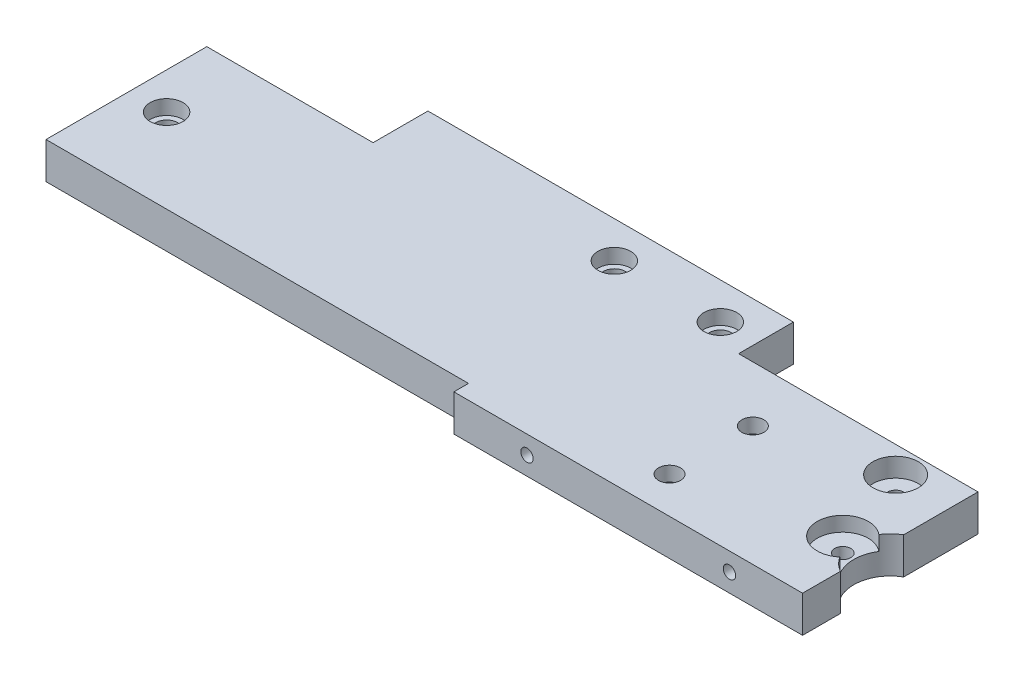
SolidWorks part; units mm, degrees
other "标注1"
sketch "草图3" plane through (0, 5, 29.5) normal (-0.6417, 0.7662, 0.0339) x (0.7661, 0.6384, 0.0747)
ref_plane "前视基准面" through (0, 0, 0) normal (0, 0, 1) x (1, 0, 0)
ref_plane "上视基准面" through (0, 0, 0) normal (0, 1, 0) x (1, 0, 0)
ref_plane "右视基准面" through (0, 0, 0) normal (1, 0, 0) x (0, 0, -1)
other "Configuration Table"
sketch "草图1" plane through (0, 0, 0) normal (0, 1, 0) x (1, 0, 0)
  line L0 (19.7074, -14.6) -> (48.9981, -14.6) construction
  line L33 (-50, -29.5) -> (0, -29.5)
  line L34 (-50, -29.5) -> (-50, 0)
  line L36 (0, -29.5) -> (0, 0)
  line L37 (-50, 0) -> (0, 0)
  line L38 (-72.75, -7.5) -> (32.75, -7.5)
  line L39 (-72.75, -7.5) -> (-72.75, -29.5)
  line L40 (-72.75, -29.5) -> (32.75, -29.5)
  line L41 (32.75, -7.5) -> (32.75, -29.5)
  line L48 (49.4474, -17.6) -> (56.141, -17.6) construction
  circle A7 centre (28.75, -22) radius 1.1
  circle A8 centre (25.0839, -11.1) radius 1.1
  circle A10 centre (25.0839, -11.1) radius 3.1
  circle A11 centre (35.25, -22) radius 5
  circle A13 centre (-19.5, -5) radius 2.25
  circle A14 centre (-19.5, -5) radius 1.5
  circle A15 centre (-5, -5) radius 1.5
  circle A16 centre (-5, -5) radius 2.25
  circle A18 centre (-67.75, -18) radius 1.5
  circle A19 centre (-67.75, -18) radius 2.25
  circle A20 centre (28.75, -22) radius 3.5
  point P0 (-90.6464, 22.0667)
  dimension "D1" = 2.2
  dimension "D2" = 29.5
  dimension "D3" = 11.5
  dimension "D4" = 50
  dimension "D5" = 6.5
  dimension "D9" = 3
  dimension "D10" = 4.5
  dimension "D13" = 6.5
  dimension "D15" = 10
  dimension "D6" = 6.2
  dimension "D17" = 7
  dimension "D7" = 4
  dimension "D8" = 2.5
  dimension "D11" = 14.5
  dimension "D12" = 5
  dimension "D14" = 5
  dimension "D16" = 5
extrude "凸台-拉伸1" add sketch "草图1" along normal blind 5 contours L34 | L37 L36 L33 L34 | L38 L41 L40 L39 region at (-61.1658, 0, 18.5164)
extrude "切除-拉伸2" cut sketch "草图1<20>" along normal through all contours A14 | A15 | A18
sketch "草图1<20>" plane through (0, 0, 0) normal (0, 1, 0) x (1, 0, 0) same geometry as "草图1"
extrude "切除-拉伸3" cut sketch "草图1<22>" against normal blind 2 from surface contours A13 | A16 | A19 starting at face at (-67.75, 5, 19.5)
sketch "草图1<22>" plane through (0, 0, 0) normal (0, 1, 0) x (1, 0, 0) same geometry as "草图1"
extrude "切除-拉伸4" cut sketch "草图1<23>" against normal blind 2.6 from surface contours A10 starting at face at (-67.75, 5, 20.25)
sketch "草图1<23>" plane through (0, 0, 0) normal (0, 1, 0) x (1, 0, 0) same geometry as "草图1"
extrude "切除-拉伸6" cut sketch "草图1<24>" against normal through all from surface contours A8 | A7 starting at face at (25.0839, 5, 14.2)
sketch "草图1<24>" plane through (0, 0, 0) normal (0, 1, 0) x (1, 0, 0) same geometry as "草图1"
sketch "草图4" plane through (0, 0, 0) normal (0, -1, 0) x (1, 0, 0)
  circle A0 centre (9.548, 15.1) radius 2.25
  circle A1 centre (9.548, 26.5) radius 2.25
  circle A2 centre (9.548, 15.1) radius 1.5
  circle A3 centre (9.548, 26.5) radius 1.5
  dimension "D1" = 3
  dimension "D2" = 4.5
extrude "切除-拉伸7" cut sketch "草图4" against normal through all contours A2 | A3
extrude "切除-拉伸8" cut sketch "草图4<3>" against normal offset from surface (3 mm away) 2 contours A1 | A0 up to face at (9.548, 5, 13.6)
sketch "草图4<3>" plane through (0, 0, 0) normal (0, -1, 0) x (1, 0, 0) same geometry as "草图4"
sketch "草图5" plane through (0, 0, 29.5) normal (0, 0, 1) x (1, 0, 0)
  line L1 (32.75, 5) -> (-14.952, 5)
  line L2 (32.75, 5) -> (32.75, 0)
  line L3 (32.75, 0) -> (-14.952, 0)
  line L4 (-14.952, 5) -> (-14.952, 0)
  dimension "D1" = 47.702
extrude "凸台-拉伸2" add sketch "草图5" along normal blind 2
sketch "草图6" plane through (0, 0, 31.5) normal (0, 0, 1) x (1, 0, 0)
  line L0 (32.75, 0) -> (32.75, 5) construction
  line L1 (-14.952, 5) -> (-14.952, 0) construction
  circle A0 centre (22.75, 2.5) radius 0.85
  circle A1 centre (-4.952, 2.5) radius 0.85
  point P11 (32.75, 2.5)
  dimension "D1" = 1.7
  dimension "D2" = 10
  dimension "D3" = 10
extrude "切除-拉伸9" cut sketch "草图6" against normal blind 4 contours A1 | A0
extrude "切除-拉伸12" cut sketch "草图1<25>" along normal through all contours A11
sketch "草图1<25>" plane through (0, 0, 0) normal (0, 1, 0) x (1, 0, 0) same geometry as "草图1"
extrude "切除-拉伸13" cut sketch "草图1<26>" against normal blind 2 from surface contours A20 starting at face at (9.548, 5, 13.6)
sketch "草图1<26>" plane through (0, 0, 0) normal (0, 1, 0) x (1, 0, 0) same geometry as "草图1"
